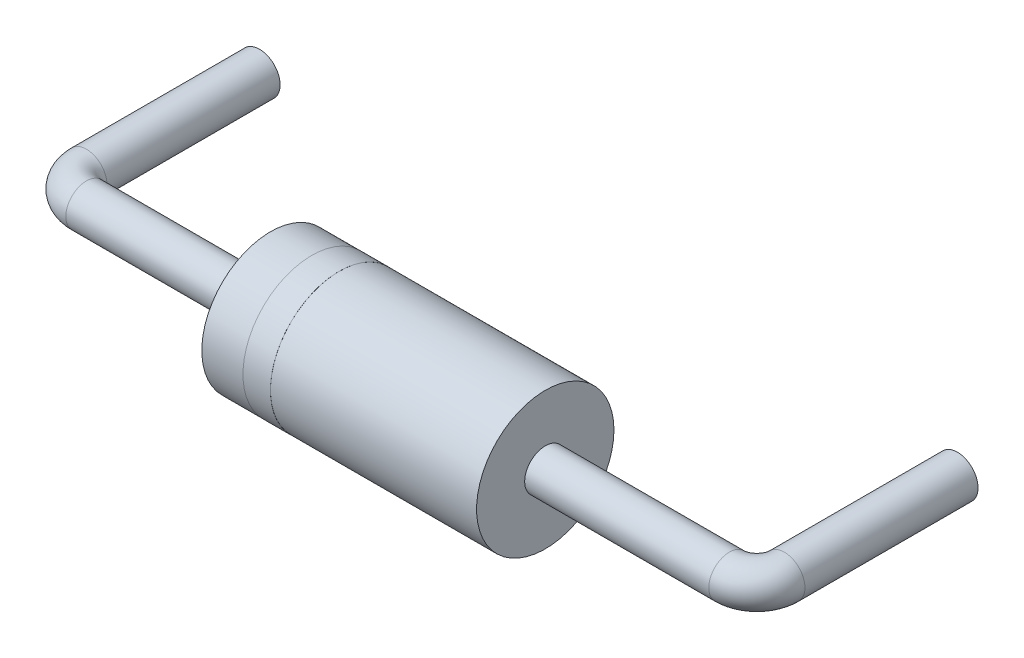
SolidWorks part; units mm, degrees
ref_plane "Ön Düzlem" through (0, 0, 0) normal (0, 0, 1) x (1, 0, 0)
ref_plane "Üst Düzlem" through (0, 0, 0) normal (0, 1, 0) x (1, 0, 0)
ref_plane "Sağ Düzlem" through (0, 0, 0) normal (1, 0, 0) x (0, 0, -1)
ref_plane "Düzlem1" through (0, 0, -2) normal (0, 0, -1) x (-1, 0, 0)
sketch "Çizim2" plane through (0, 0, -2) normal (0, 0, -1) x (-1, 0, 0)
  line L0 (-5.08, 0) -> (5.08, 0) construction
  circle A0 centre (-5.08, 0) radius 0.3
  dimension "D2" = 0.6
  dimension "D1" = 10.16
sketch "Çizim3" plane through (0, 0, 0) normal (0, 1, 0) x (1, 0, 0)
  line L0 (5.08, 2) -> (5.08, -0.52)
  line L1 (4.68, -0.92) -> (-4.68, -0.92)
  line L2 (-5.08, -0.52) -> (-5.08, 2)
  line L3 (5.08, 2) -> (-5.08, 2) construction
  line L4 (0.9911, 2) -> (-0.9911, 2) construction
  arc A0 (-4.68, -0.92) -> (-5.08, -0.52) centre (-4.68, -0.52) cw
  arc A1 (5.08, -0.52) -> (4.68, -0.92) centre (4.68, -0.52) cw
  point P12 (5.08, 2)
  dimension "D2" = 0.4
  dimension "D1" = 2.92
sweep "Süpür2" add profiles "Çizim2" path "Çizim3"
sketch "Çizim4" plane through (0, 0, 0) normal (1, 0, 0) x (0, 0, -1)
  circle A0 centre (-0.92, 0) radius 1
  dimension "D1" = 2
extrude "Yükseklik-Ekstrüzyon3" add sketch "Çizim4" against normal mid plane 4 contours A0
sketch "Çizim7" plane through (0, 0, 0) normal (-1, 0, 0) x (0, 0, 1)
  circle A0 centre (0.92, 0) radius 0.5
  dimension "D1" = 1
extrude "Ekstrüzyon-İnce1" add sketch "Çizim4<5>" along normal mid plane 0.4 from offset 1.2 thin contours A0 offset against normal yes thin type one direction wall 0.001
sketch "Çizim4<5>" plane through (0, 0, 0) normal (1, 0, 0) x (0, 0, -1) same geometry as "Çizim4"
